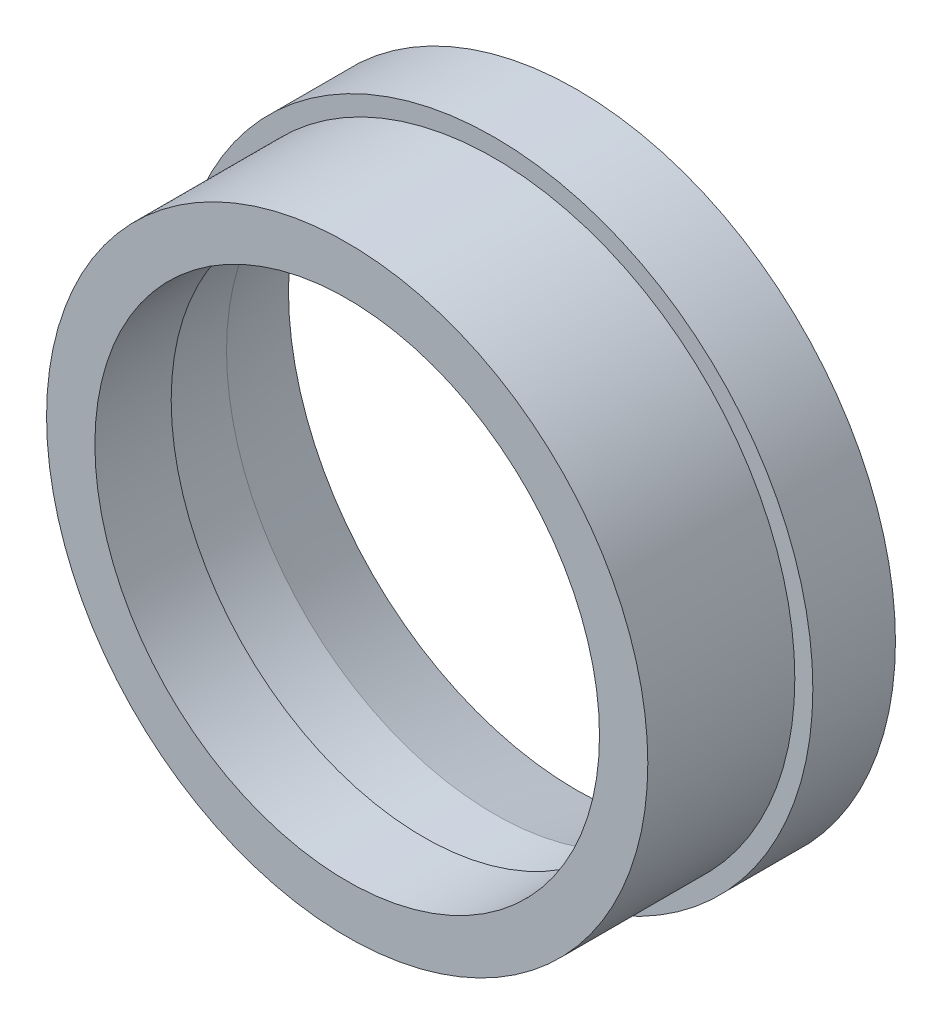
SolidWorks part; units mm, degrees
material "6061-T6 (SS)"
ref_plane "Front Plane" through (0, 0, 0) normal (0, 0, 1) x (1, 0, 0)
ref_plane "Top Plane" through (0, 0, 0) normal (0, 1, 0) x (1, 0, 0)
ref_plane "Right Plane" through (0, 0, 0) normal (1, 0, 0) x (0, 0, -1)
sketch "Sketch1" plane through (0, 0, 0) normal (0, 0, 1) x (1, 0, 0)
  circle A0 centre (0, 0) radius 49
  circle A1 centre (0, 0) radius 38.7985
  dimension "D1" = 77.597
  dimension "D2" = 98
extrude "Extrude1" add sketch "Sketch1" along normal blind 35.306
sketch "Sketch2" plane through (0, 0, 35.306) normal (0, 0, 1) x (1, 0, 0)
  circle A0 centre (0, 0) radius 46.228
extrude "Extrude2" cut sketch "Sketch2" against normal blind 22.606 flip side to cut
sketch "Sketch3" plane through (0, 0, 0) normal (0, 0, -1) x (-1, 0, 0)
  circle A0 centre (0, 0) radius 41.1607
  dimension "D1" = 82.3214
extrude "Extrude3" cut sketch "Sketch3" against normal blind 23.5712
chamfer "Chamfer1" distance 3.175 distance2 12.7 1 edges at (-41.1607, 0, 0) first distance on face at (-41.1607, 0, 0)
